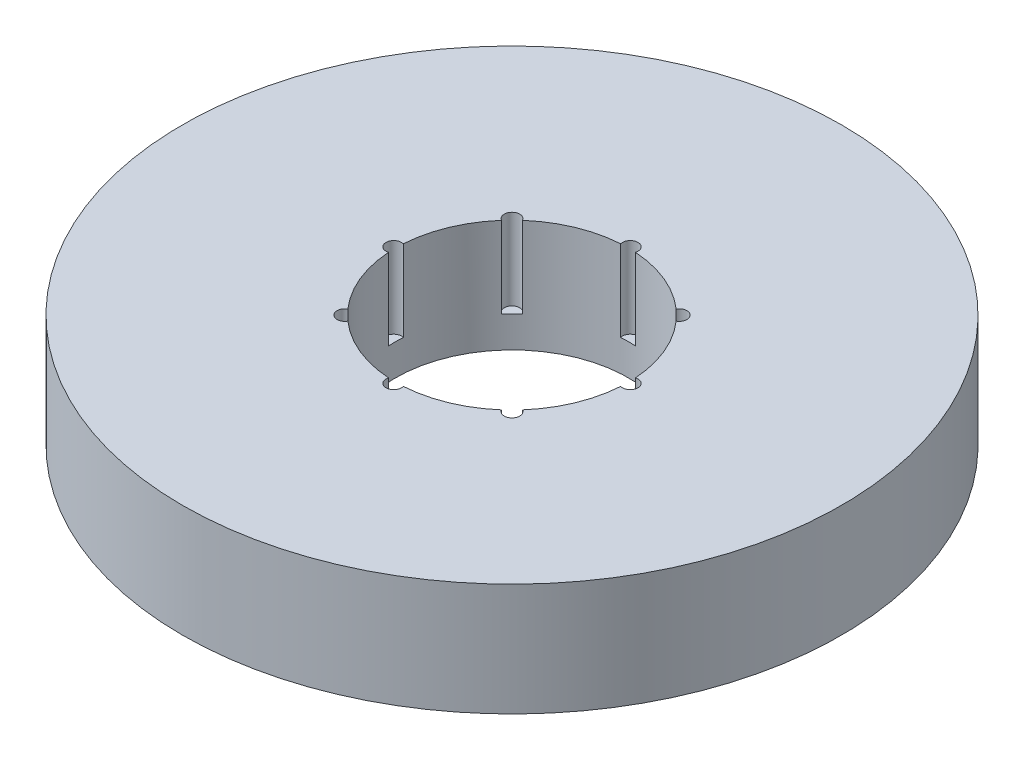
SolidWorks part; units mm, degrees
ref_plane "Front Plane" through (0, 0, 0) normal (0, 0, 1) x (1, 0, 0)
ref_plane "Top Plane" through (0, 0, 0) normal (0, 1, 0) x (1, 0, 0)
ref_plane "Right Plane" through (0, 0, 0) normal (1, 0, 0) x (0, 0, -1)
sketch "Sketch1" plane through (0, 0, 0) normal (0, 1, 0) x (1, 0, 0)
  circle A0 centre (0, 0) radius 85
  dimension "FLANGE_OD" = 170
extrude "Boss-Extrude1" add sketch "Sketch1" along normal blind 29
sketch "Sketch2" plane through (0, 0, 0) normal (0, 1, 0) x (1, 0, 0)
  circle A0 centre (0, 0) radius 30
  dimension "BORE_D" = 60
extrude "Cut-Extrude1" cut sketch "Sketch2" along normal through all
sketch "Sketch3" plane through (0, 29, 0) normal (0, 1, 0) x (1, 0, 0)
  circle A0 centre (0, 0) radius 30.5015 construction
  circle A1 centre (-30.5015, 0) radius 1.9862
  dimension "BOLT_D" = 3.9725
  dimension "BOLT_PCD" = 61.0029
extrude "Cut-Extrude2" cut sketch "Sketch3" against normal blind 20.9216
pattern_circular "CirPattern1" count 8 over 360 about axis through (0, 0, 0) along (0, 1, 0) of "Cut-Extrude2"
